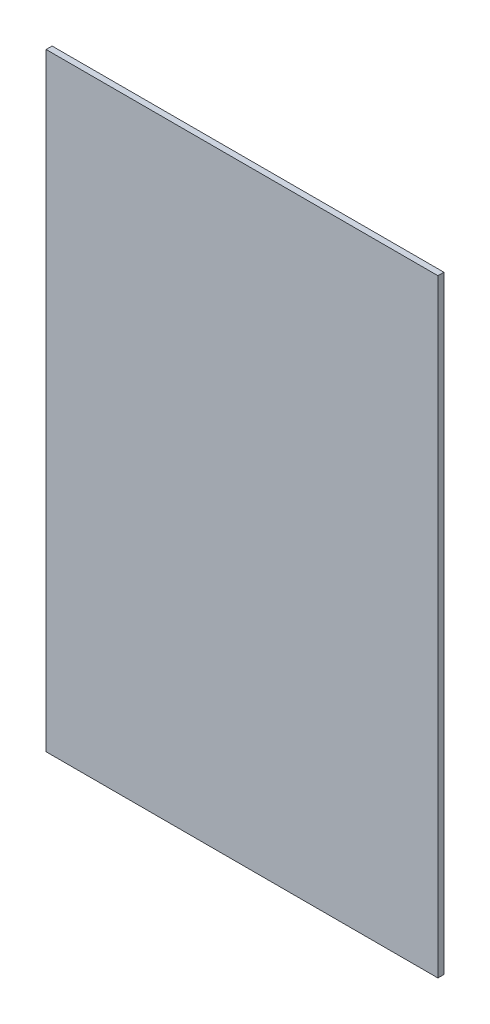
SolidWorks part; units mm, degrees
ref_plane "Спереди" through (0, 0, 0) normal (0, 0, 1) x (1, 0, 0)
ref_plane "Сверху" through (0, 0, 0) normal (0, 1, 0) x (1, 0, 0)
ref_plane "Справа" through (0, 0, 0) normal (1, 0, 0) x (0, 0, -1)
other "Configuration Table"
sketch "Эскиз1" plane through (0, 0, 0) normal (0, 0, 1) x (1, 0, 0)
  line L2 (-1162.3, -506.285) -> (-510, -506.285)
  line L3 (-1162.3, -506.285) -> (-1162.3, 506.285)
  line L4 (-1162.3, 506.285) -> (-510, 506.285)
  line L5 (-510, -506.285) -> (-510, 506.285)
extrude "Бобышка-Вытянуть1" add sketch "Эскиз1" along normal blind 10
equation "\"Глубина груза\"= 490"
equation "\"Высота груза\"= 297"
equation "\"Ширина ячейки\"= \"Ширина груза\" + 10"
equation "\"Глубина ячейки\"= \"Глубина груза\" + 10"
equation "\"Высота ячейки\"= \"Высота груза\" + 10 + 13"
equation "\"Колво ячеек ширина\"= 2"
equation "\"Колво ячеек высота\"= 2"
equation "\"Толщина стенки\"= 10"
equation "\"Крепление дверцы\"= 5"
equation "\"Ширина рейки\"= \"Толщина шестерни\""
equation "\"Высота рейки\"= 20"
equation "\"Высота пола\"= 20"
equation "\"Колво полозьев\"= 5"
equation "\"Отступ рейки\"= 20"
equation "\"Глубина каретки\"= \"Глубина ячейки\" + 30 + \"Мотор Y высота корпуса\" + 20"
equation "\"Длинна рейки\"= ( \"Ширина ячейки\" + \"Толщина стенки\" + \"Крепление дверцы\" ) * \"Колво ячеек ширина\" + \"Ширина ячейки выгрузки\" * \"Колво выгрузки\" + \"Толщина стенки\""
equation "\"Отступ шпильки\"= 26"
equation "\"Диаметр шпильки\"= 5"
equation "\"Длинна шпильки\"= ( \"Высота ячейки\" + \"Толщина стенки\" + \"Высота пола\" ) * \"Колво ячеек высота\" + ( \"Толщина стенки\" + \"Отступ рейки\" ) * 2 "
equation "\"Ширина пластины\"= 50  "
equation "\"Высота зона выгрузки\"= \"Высота ячейки\" * 2 + \"Толщина стенки\" * 2"
equation "\"Колво выгрузки\"= 1"
equation "\"Ширина ячейки выгрузки\"= \"Ширина ячейки\" + \"Толщина стенки\" + \"Отступ крепления мотора фиксации\"*2"
equation "\"Отступ крепления мотора фиксации\" = 30"
equation "\"Мотор X ширина корпуса\"= 42.3"
equation "\"Мотор X высота корпуса\"= 42.3"
equation "\"Мотор X длина корпуса\"= 40"
equation "\"Мотор X вылет вала\"= 19.8"
equation "\"Мотор Y ширина корпуса\"= 42.3"
equation "\"Мотор Y высота корпуса\"= 42.3"
equation "\"Мотор Y длина корпуса\"= 48"
equation "\"Мотор Y вылет вала\"= 30"
equation "\"Мотор Z ширина корпуса\"= 42"
equation "\"Мотор Z высота корпуса\"= 42"
equation "\"Мотор Z длина корпуса\"= 40"
equation "\"Мотор Z вылет вала\"= 23"
equation "\"Мотор диаметр вала ПРЕДВ\"= 5"
equation "\"Мотор шаг крепления ПРЕДВ\"= 31"
equation "\"Мотор диаметр отверстий ПРЕДВ\"= 3"
equation "\"Мотор глубина отверстий ПРЕДВ\"= 4.5"
equation "\"Мотор диаметр буртика ПРЕДВ\"= 22"
equation "\"Мотор высота буртика ПРЕДВ\"= 2"
equation "\"Мотор диаметр шкива ПРЕДВ\"= 16"
equation "\"Мотор длина шкива ПРЕДВ\"= 12"
equation "\"Мотор отступ шкива ПРЕДВ\"= 5"
equation "\"Мотор X шаг градусов\"= 1.8"
equation "\"Мотор Y шаг градусов\"= 1.8"
equation "\"Мотор Z шаг градусов\"= 1.8"
equation "\"Мотор Y диаметр ротора\"= 25.78"
equation "\"Толщина шестерни\"= 10"
equation "\"Ширина груза\"= 420"
equation "\"D1@Бобышка-Вытянуть1\"=\"Толщина стенки\""
